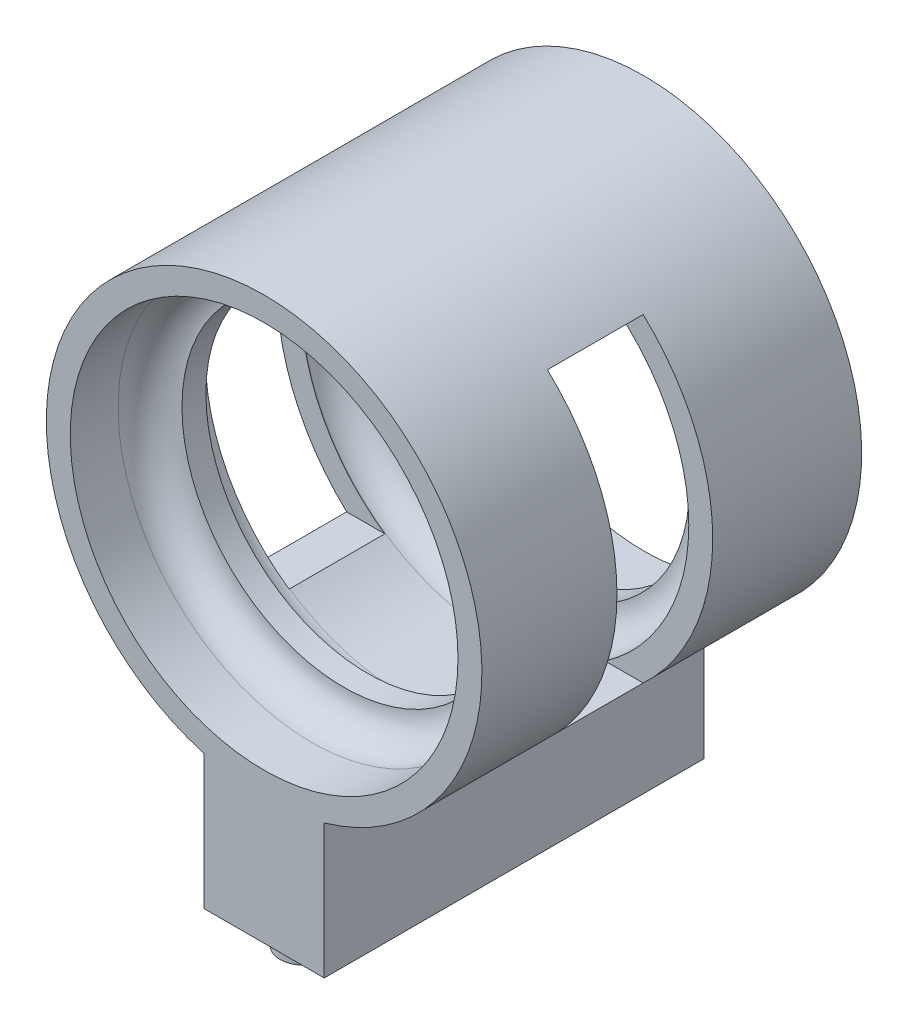
SolidWorks part; units mm, degrees
ref_plane "Front Plane" through (0, 0, 0) normal (0, 0, 1) x (1, 0, 0)
ref_plane "Top Plane" through (0, 0, 0) normal (0, 1, 0) x (1, 0, 0)
ref_plane "Right Plane" through (0, 0, 0) normal (1, 0, 0) x (0, 0, -1)
sketch "Sketch1" plane through (0, 0, 0) normal (0, 0, 1) x (1, 0, 0)
  line L0 (-3.7667, -13.12) -> (3.7667, -13.12)
  line L1 (0, -55) -> (0, 55) construction
  line L2 (0, -13.65) -> (6.7961, -13.65) construction
  circle A0 centre (0, 0) radius 12.15
  circle A1 centre (0, 0) radius 13.65
  point P6 (0, -13.12)
  dimension "D1" = 24.3
  dimension "D2" = 27.3
  dimension "D3" = 0.53
extrude "Boss-Extrude1" add sketch "Sketch1" along normal blind 23.8 contours L0 A1 A0 region at (-7.983, 10.5973, 0)
sketch "Sketch2" plane through (0, 0, 23.8) normal (0, 0, 1) x (1, 0, 0)
  circle A1 centre (0, 0) radius 12.15
  circle A2 centre (0, 0) radius 10.15
  circle A3 centre (0, 0) radius 10.15
  dimension "D1" = 2
extrude "Boss-Extrude2" add sketch "Sketch2" against normal blind 1.5 from offset 5 offset against normal yes
extrude "Boss-Extrude3" add sketch "Sketch2<2>" along normal blind 1.5 from offset 18 offset against normal yes
sketch "Sketch2<2>" plane through (0, 0, 23.8) normal (0, 0, 1) x (1, 0, 0) same geometry as "Sketch2"
sketch "Sketch4" plane through (0, 0, 0) normal (1, 0, 0) x (0, 0, -1)
  line L0 (13.09, 0) -> (-13.09, 0) construction
  line L1 (-15.3358, -10) -> (-9.3358, -10)
  line L2 (-15.3358, -10) -> (-15.3358, 10)
  line L3 (-15.3358, 10) -> (-9.3358, 10)
  line L4 (-9.3358, -10) -> (-9.3358, 10)
  line L5 (-15.3358, -10) -> (-9.3358, 10) construction
  line L6 (-15.3358, 10) -> (-9.3358, -10) construction
  point P0 (-12.3358, 0)
  dimension "D1" = 20
  dimension "D2" = 6
extrude "Cut-Extrude1" cut sketch "Sketch4" against normal through all both and the other way through all
sketch "Sketch5" plane through (0, -13.12, 0) normal (0, -1, 0) x (1, 0, 0)
  line L0 (0, 23.8) -> (0, 0) construction
  line L1 (-3.7667, 23.8) -> (3.7667, 23.8) construction
  line L2 (0, 21.3) -> (0, 2.5) construction
  circle A0 centre (0, 21.3) radius 1.5
  circle A1 centre (0, 2.5) radius 1.5
  point P7 (0, 11.9)
  point P8 (0, 11.9)
  dimension "D2" = 3
  dimension "D3" = 3
  dimension "D1" = 18.8
extrude "Boss-Extrude4" add sketch "Sketch5" along normal blind 9.8
fillet "Fillet1" radius 2 4 edges at (12.15, 0, 5.8) (12.15, 0, 7.3) (12.15, 0, 17.3) (12.15, 0, 18.8)
sketch "Sketch7" plane through (0, -13.12, 0) normal (0, -1, 0) x (1, 0, 0)
  line L0 (15.015, 0) -> (-15.015, 0) construction
  line L1 (-3.7667, 23.8) -> (3.7667, 23.8)
  line L2 (-3.7667, 23.8) -> (-3.7667, 0)
  line L3 (-3.7667, 0) -> (3.7667, 0)
  line L4 (3.7667, 23.8) -> (3.7667, 0)
  line L5 (3.7667, 23.8) -> (3.7667, 0) construction
extrude "Boss-Extrude5" add sketch "Sketch7" along normal blind 8.42
